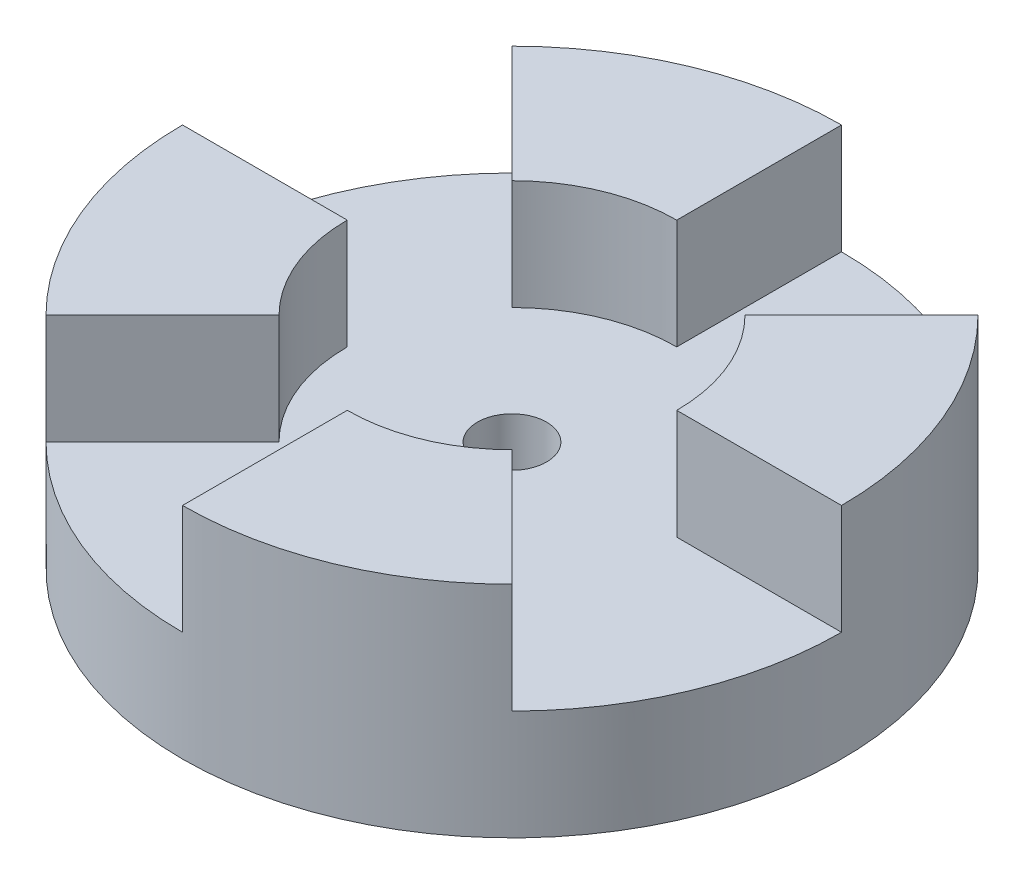
SolidWorks part; units mm, degrees
ref_plane "Front Plane" through (0, 0, 0) normal (0, 0, 1) x (1, 0, 0)
ref_plane "Top Plane" through (0, 0, 0) normal (0, 1, 0) x (1, 0, 0)
ref_plane "Right Plane" through (0, 0, 0) normal (1, 0, 0) x (0, 0, -1)
sketch "Sketch1" plane through (0, 0, 0) normal (0, 1, 0) x (1, 0, 0)
  circle A0 centre (-80.7899, -8.4156) radius 38.1
extrude "Boss-Extrude1" add sketch "Sketch1" along normal blind 12.7
sketch "Sketch2" plane through (0, 12.7, 0) normal (0, 1, 0) x (1, 0, 0)
  circle A0 centre (-80.7899, -8.4156) radius 4.0005
extrude "Cut-Extrude1" cut sketch "Sketch2" against normal blind 12.7
sketch "Sketch3" plane through (0, 12.7, 0) normal (0, 1, 0) x (1, 0, 0)
  line L0 (-67.3195, 5.0548) -> (-53.8491, 18.5252)
  line L1 (-94.2602, 5.0548) -> (-107.7306, 18.5252)
  line L2 (-94.2602, -21.886) -> (-107.7306, -35.3564)
  line L3 (-67.3195, -21.886) -> (-53.8491, -35.3564)
  line L4 (-99.8399, -8.4156) -> (-118.8899, -8.4156)
  line L5 (-80.7899, 10.6344) -> (-80.7899, 29.6844)
  line L6 (-61.7399, -8.4156) -> (-42.6899, -8.4156)
  line L7 (-80.7899, -27.4656) -> (-80.7899, -46.5156)
  arc A1 (-80.7899, 10.6344) -> (-61.7399, -8.4156) centre (-80.7899, -8.4156) cw
  arc A2 (-80.7899, 10.6344) -> (-61.7399, -8.4156) centre (-80.7899, -8.4156) cw
  circle A3 centre (-80.7899, -8.4156) radius 38.1 construction
  arc A4 (-80.7899, 10.6344) -> (-99.8399, -8.4156) centre (-80.7899, -8.4156) ccw
  arc A5 (-99.8399, -8.4156) -> (-80.7899, -27.4656) centre (-80.7899, -8.4156) ccw
  arc A6 (-80.7899, -27.4656) -> (-61.7399, -8.4156) centre (-80.7899, -8.4156) ccw
  circle M2 centre (-80.7899, -8.4156) radius 38.1
extrude "Boss-Extrude2" add sketch "Sketch3" along normal blind 12.7 contours A4 L5 L1 M2 | L0 A1 L6 M2 | A6 L7 L3 M2 | A5 L4 L2 M2 region at (-54.1105, 12.7, -2.6353) region at (-91.8408, 12.7, -18.2638) region at (-69.7389, 12.7, 35.095) region at (-107.4692, 12.7, 19.4666)
sketch "Sketch5" plane through (0, 0, 0) normal (0, -1, 0) x (1, 0, 0)
  circle A0 centre (-80.7899, 8.4156) radius 5.334
extrude "Cut-Extrude2" cut sketch "Sketch5" against normal blind 2.54
